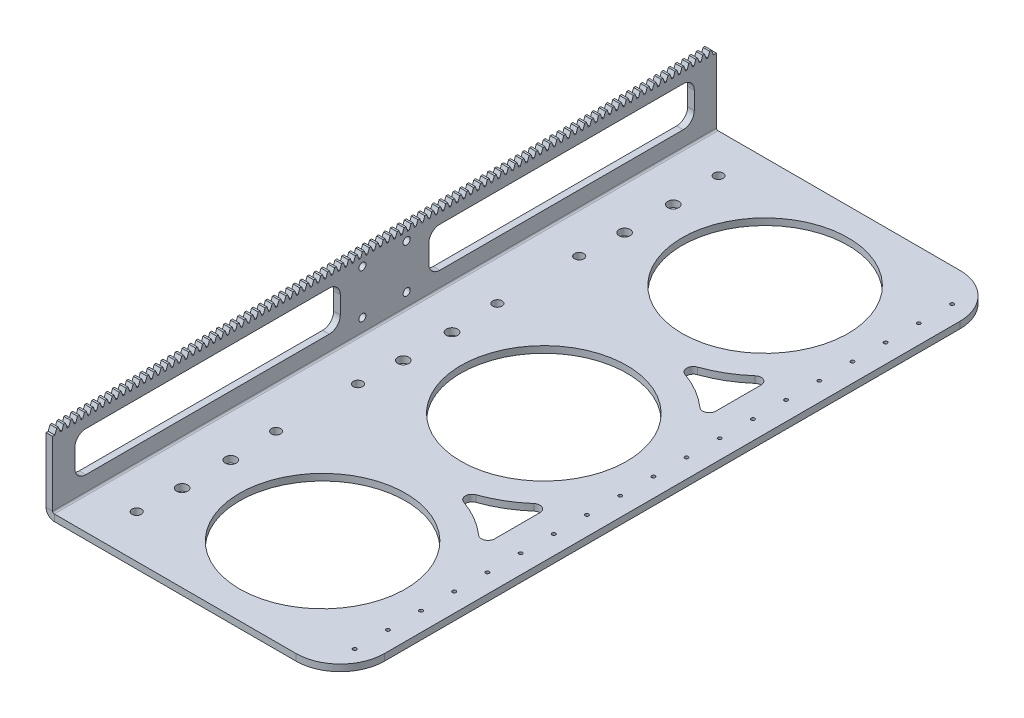
SolidWorks part; units mm, degrees
note: The reader was unsure of these and kept them because the rebuilt part matched: thickness of "基材-凸緣2", "鈑金4", "鈑金6", "鈑金13", "鈑金14", "鈑金15", "鈑金16", "鈑金17", "鈑金18", "鈑金19", "鈑金20", "鈑金21", "鈑金22"; bend radius of "基材彎折1".
material "AISI 304"
ref_plane "前基準面" through (0, 0, 0) normal (0, 0, 1) x (1, 0, 0)
ref_plane "上基準面" through (0, 0, 0) normal (0, 1, 0) x (1, 0, 0)
ref_plane "右基準面" through (0, 0, 0) normal (1, 0, 0) x (0, 0, -1)
sketch "草圖8" plane through (0, 0, 0) normal (0, 0, 1) x (1, 0, 0)
  line L0 (0, 0) -> (0, 30)
  line L1 (0, 0) -> (130, 0)
  dimension "D1" = 130
  dimension "D2" = 30
base flange "基材-凸緣2" sketch "草圖8" end condition mid plane depth 300 reverse direction no thickness 3 reverse thickness direction no bend radius 0.7366
bend "基材彎折1" bend radius 0.7366 bend angle 90 parameters "D5"=1
sketch "草圖18" plane through (-3, 0, 0) normal (-1, 0, 0) x (0, 0, 1)
  line L0 (149, 30) -> (148.1811, 32.25)
  line L1 (148.1811, 32.25) -> (147.3382, 32.25)
  line L2 (147.3382, 32.25) -> (146.5193, 30)
  line L3 (150, 30) -> (-150, 30) construction
  line L4 (146.5193, 30) -> (149, 30)
  line L5 (148.545, 31.25) -> (146.9742, 31.25) construction
  line L7 (150, 30) -> (-150, 30) construction
  dimension "D1" = 2.25
  dimension "D2" = 40
  dimension "D4" = 1.5708
  dimension "D3" = 1
  dimension "D5" = 1
extrude "填料-伸長1" add sketch "草圖18" against normal up to surface (3 mm away) up to face at (0, 15.3683, 0)
sketch "草圖12" plane through (0, 0, 0) normal (0, 1, 0) x (1, 0, 0)
  line L0 (72, 0) -> (130, 0) construction
  line L3 (130, -150) -> (130, 150) construction
  circle A0 centre (72, 0) radius 37.5
  dimension "D1" = 75
  dimension "D2" = 58
extrude "除料-伸長2" cut sketch "草圖12" against normal through all normal cut yes
hole_wizard "M3 餘隙孔1" positions "草圖15" profile "草圖16" hole size "M3" standard "Ansi Metric" end condition through all
sketch "草圖15" plane through (0, 0, 0) normal (1, 0, 0) x (0, 0, -1)
  line L1 (-10, 6.5) -> (10, 6.5) construction
  line L2 (-10, 6.5) -> (-10, 26.5) construction
  line L3 (-10, 26.5) -> (10, 26.5) construction
  line L4 (10, 6.5) -> (10, 26.5) construction
  line L5 (-10, 6.5) -> (10, 26.5) construction
  line L6 (-10, 26.5) -> (10, 6.5) construction
  line L9 (-150, 0.7366) -> (150, 0.7366) construction
  line L10 (0, 0.7366) -> (0, 16.5) construction
  line L12 (-150, 30) -> (-149, 30) construction
  point P2 (10, 26.5)
  point P42 (-10, 26.5)
  point P43 (10, 6.5)
  point P60 (-10, 6.5)
  dimension "D1" = 20
  dimension "D2" = 20
  dimension "D3" = 13.5
sketch "草圖16" plane through (0, 26.5, -10) normal (0, 1, 0) x (0, 0, -1)
  line L0 (0, 0) -> (0, 3)
  line L1 (0, 3) -> (1.6, 3)
  line L2 (1.6, 3) -> (1.6, 0)
  line L5 (1.6, 0) -> (0, 0)
  line L11 (0, -6.35) -> (0, 107.95) construction
  dimension "貫穿孔直徑" = 3.2
  dimension "貫穿孔深度" = 3
pattern_linear "直線複製排列3" count 95 spacing 3.14 along (0, 0, -1) of "填料-伸長1"
pattern_linear "直線複製排列4" count 2 spacing 100 along (0, 0, -1) count 2 spacing 100 along (0, 0, 1) of "除料-伸長2" pattern seed only yes
sketch "草圖19" plane through (0, 0, 0) normal (0, 1, 0) x (1, 0, 0)
  line L3 (130, -150) -> (130, 150) construction
  line L7 (110, 67.5038) -> (110, 32.4962)
  arc A4 (110, 32.4962) -> (72, 50) centre (72, 0) ccw
  arc A5 (110, 67.5038) -> (72, 50) centre (72, 100) cw
  point P6 (0, 0)
  dimension "D2" = 20
extrude "除料-伸長3" cut sketch "草圖19" against normal through all contours L7 A4 A5 normal cut yes
sketch "草圖20" plane through (0, 0, 0) normal (1, 0, 0) x (0, 0, -1)
  line L0 (10, 26.5) -> (10, 6.5) construction
  line L1 (10, 16.5) -> (80, 16.5) construction
  line L2 (150, 30) -> (150, 0.7366) construction
  line L3 (20, 7.5) -> (140, 7.5)
  line L4 (20, 7.5) -> (20, 25.5)
  line L5 (20, 25.5) -> (140, 25.5)
  line L6 (140, 7.5) -> (140, 25.5)
  line L7 (20, 7.5) -> (140, 25.5) construction
  line L8 (20, 25.5) -> (140, 7.5) construction
  dimension "D1" = 10
  dimension "D2" = 120
  dimension "D3" = 18
extrude "除料-伸長4" cut sketch "草圖20" against normal through all normal cut yes
fillet "圓角2" radius 5 4 edges at (-1.5, 25.5, -20) (-1.5, 7.5, -20) (-1.5, 25.5, -140) (-1.5, 7.5, -140)
mirror "鏡射1" about plane through (0, 0, 0) normal (0, 0, 1) of "除料-伸長4", "除料-伸長3", "圓角2"
sketch "草圖21" plane through (0, -3, 0) normal (0, -1, 0) x (1, 0, 0)
  line L0 (19.5, -111) -> (19.5, -89) construction
  line L1 (72, -100) -> (19.5, -100) construction
  line L2 (19.5, -11) -> (19.5, 11) construction
  line L3 (72, 0) -> (19.5, 0) construction
  line L4 (72, 100) -> (19.5, 100) construction
  line L5 (19.5, 111) -> (19.5, 89) construction
  circle A0 centre (19.5, -111) radius 2.5
  circle A1 centre (19.5, -89) radius 2.5
  circle A2 centre (19.5, 11) radius 2.5
  circle A3 centre (19.5, -11) radius 2.5
  circle A4 centre (19.5, 111) radius 2.5
  circle A5 centre (19.5, 89) radius 2.5
  dimension "D1" = 5
  dimension "D2" = 22
  dimension "D3" = 52.5
  dimension "D4" = 3
extrude "除料-伸長5" cut sketch "草圖21" against normal blind 10 normal cut yes
hole_wizard "M4 螺旋的螺孔鑽1" positions "草圖22" profile "草圖23" hole size "M4x0.7" standard "Ansi Metric"
sketch "草圖22" plane through (0, -3, 0) normal (0, -1, 0) x (-1, 0, 0)
  line L0 (-18.5, 132.5) -> (-19.5, 132.5) construction
  line L1 (-19.5, 132.5) -> (-19.5, 111) construction
  line L5 (-18.5, 132.5) -> (-18.5, 69.5) construction
  line L9 (-19.5, 11) -> (-19.5, -11) construction
  line L10 (-18.5, -67.5) -> (-18.5, -130.5) construction
  line L13 (-19.5, -89) -> (-19.5, -111) construction
  line L14 (-18.5, 32.5) -> (-18.5, -30.5) construction
  point P0 (-18.5, 132.5)
  point P16 (-18.5, 69.5)
  point P29 (-18.5, 32.5)
  point P30 (-18.5, -30.5)
  point P56 (-18.5, -67.5)
  point P57 (-18.5, -130.5)
  dimension "D1" = 1
  dimension "D2" = 21.5
  dimension "D3" = 63
  dimension "D5" = 63
  dimension "D6" = 21.5
  dimension "D7" = 1
  dimension "D4" = 21.5
  dimension "D8" = 63
  dimension "D9" = 1
sketch "草圖23" plane through (18.5, -3, -132.5) normal (1, 0, 0) x (0, 0, -1)
  line L0 (0, 0) -> (0, 21.2618)
  line L1 (0, 21.2618) -> (2.1, 20)
  line L2 (2.1, 20) -> (2.1, 0)
  line L5 (2.1, 0) -> (0, 0)
  line L10 (0, 21.2618) -> (-2.1, 20) construction
  line L11 (0, -6.35) -> (0, 107.95) construction
  dimension "鑽孔直徑" = 4.2
  dimension "鑽孔深度" = 20
  dimension "導頭角度" = 118
fillet "圓角3" radius 3 6 edges at (110, -1.5, -32.4962) (110, -1.5, -67.5038) (72, -1.5, -50) (110, -1.5, 32.4962) (72, -1.5, 50) (110, -1.5, 67.5038)
fillet "圓角4" radius 20 2 edges at (130, -1.5, -150) (130, -1.5, 150)
hole_wizard "M2x0.4 螺紋孔1" positions "草圖25" profile "草圖26" tap size "M2x0.4" standard "Ansi Metric" end condition through all
sketch "草圖25" plane through (0, -3, 0) normal (0, -1, 0) x (-1, 0, 0)
  line L0 (-121.5, -135) -> (-121.5, 135) construction
  line L3 (-130, -130) -> (-130, 130) construction
  line L4 (-0.7366, -150) -> (-110, -150) construction
  point P1 (-121.5, -135)
  point P16 (-121.5, -120)
  point P17 (-121.5, -105)
  point P18 (-121.5, -90)
  point P19 (-121.5, -75)
  point P20 (-121.5, -60)
  point P21 (-121.5, -45)
  point P22 (-121.5, -30)
  point P23 (-121.5, -15)
  point P24 (-121.5, 0)
  point P25 (-121.5, 15)
  point P26 (-121.5, 30)
  point P27 (-121.5, 45)
  point P28 (-121.5, 60)
  point P29 (-121.5, 75)
  point P30 (-121.5, 90)
  point P31 (-121.5, 105)
  point P32 (-121.5, 120)
  point P33 (-121.5, 135)
  dimension "D1" = 8.5
  dimension "D2" = 15
  dimension "D3" = 270
  dimension "D5" = 15
  dimension "D4" = 19
sketch "草圖26" plane through (121.5, -3, 135) normal (1, 0, 0) x (0, 0, -1)
  line L0 (0, 0) -> (0, 35.25)
  line L1 (0, 35.25) -> (0.8, 35.25)
  line L2 (0.8, 35.25) -> (0.8, 0)
  line L5 (0.8, 0) -> (0, 0)
  line L11 (0, -6.35) -> (0, 107.95) construction
  dimension "貫穿螺孔鑽直徑" = 1.6
  dimension "貫穿螺孔鑽深度" = 35.25
sketch "彎折-線1" [suppressed] plane through (0, 0, 0) normal (0, 1, 0) x (1, 0, 0)
sketch "邊界方塊1" [suppressed] plane through (0, 0, 0) normal (0, 1, 0) x (1, 0, 0)
sheet metal parameters "鈑金4" thickness 3 parameters "D1"=0.7366
flat pattern "平板-型式4" [suppressed]
sketch "彎折-線3" plane through (0, 0, 0) normal (0, 1, 0) x (1, 0, 0)
  line L0 (-1.02, -150) -> (-1.02, 150) construction
  line L1 (-1.02, -150) -> (-1.02, 150) construction
sketch3d "邊界方塊3" [suppressed]
  line L0 (-32.04, 300, 0) -> (-32.04, 0, 0) construction
  line L1 (120, 300, 0) -> (120, 0, 0) construction
  line L2 (-32.04, 300, 0) -> (120, 300, 0) construction
  line L3 (-32.04, 0, 0) -> (120, 0, 0) construction
bend of the flat pattern "平板-<基材彎折1>1"
sheet metal parameters "鈑金6" thickness 3 parameters "D1"=0.7366
flat pattern "平板-型式4"
sketch "彎折-線3" plane through (0, 0, 0) normal (0, 1, 0) x (1, 0, 0)
  line L0 (-1.02, -150) -> (-1.02, 150) construction
  line L1 (-1.02, -150) -> (-1.02, 150) construction
sketch3d "邊界方塊3" [suppressed]
  line L0 (120.0001, 300, 0) -> (120, 0, 0) construction
  line L1 (-34.29, 300, 0) -> (-34.29, 0, 0) construction
  line L2 (120.0001, 300, 0) -> (-34.29, 300, 0) construction
  line L3 (120, 0, 0) -> (-34.29, 0, 0) construction
bend of the flat pattern "平板-<基材彎折1>1"
sheet metal parameters "鈑金13" thickness 3 parameters "D1"=0.7366
flat pattern "平板-型式4"
sketch "彎折-線3" plane through (0, 0, 0) normal (0, 1, 0) x (1, 0, 0)
  line L0 (-1.8054, -165) -> (-1.8054, 165) construction
  line L1 (-1.8054, -165) -> (-1.8054, 165) construction
sketch3d "邊界方塊3" [suppressed]
  line L0 (-33.6108, 330, 0) -> (-33.6108, 0, 0) construction
  line L1 (150, 330, 0) -> (150, 0, 0) construction
  line L2 (-33.6108, 330, 0) -> (150, 330, 0) construction
  line L3 (-33.6108, 0, 0) -> (150, 0, 0) construction
bend of the flat pattern "平板-<基材彎折1>1"
sheet metal parameters "鈑金14" thickness 3 parameters "D1"=0.7366
flat pattern "平板-型式4"
sketch "彎折-線3" plane through (0, 0, 0) normal (0, 1, 0) x (1, 0, 0)
  line L0 (-1.02, -150) -> (-1.02, 150) construction
  line L1 (-1.02, -150) -> (-1.02, 150) construction
sketch3d "邊界方塊3" [suppressed]
  line L0 (120.0001, 300, 0) -> (120, 0, 0) construction
  line L1 (-34.29, 300, 0) -> (-34.29, 0, 0) construction
  line L2 (120.0001, 300, 0) -> (-34.29, 300, 0) construction
  line L3 (120, 0, 0) -> (-34.29, 0, 0) construction
bend of the flat pattern "平板-<基材彎折1>1"
sheet metal parameters "鈑金15" thickness 3 parameters "D1"=0.7366
flat pattern "平板-型式4"
sketch "彎折-線3" plane through (0, 0, 0) normal (0, 1, 0) x (1, 0, 0)
  line L0 (-1.02, -150) -> (-1.02, 150) construction
  line L1 (-1.02, -150) -> (-1.02, 150) construction
sketch3d "邊界方塊3" [suppressed]
  line L0 (-34.29, 300, 0) -> (-34.29, 0, 0) construction
  line L1 (120, 300, 0) -> (120, 0, 0) construction
  line L2 (-34.29, 300, 0) -> (120, 300, 0) construction
  line L3 (-34.29, 0, 0) -> (120, 0, 0) construction
bend of the flat pattern "平板-<基材彎折1>1"
sheet metal parameters "鈑金16" thickness 3 parameters "D1"=0.7366
flat pattern "平板-型式4"
sketch "彎折-線3" plane through (0, 0, 0) normal (0, 1, 0) x (1, 0, 0)
  line L0 (-1.02, -150) -> (-1.02, 150) construction
  line L1 (-1.02, -150) -> (-1.02, 150) construction
sketch3d "邊界方塊3" [suppressed]
  line L0 (-34.29, 300, 0) -> (-34.29, 0, 0) construction
  line L1 (120, 300, 0) -> (120, 0, 0) construction
  line L2 (-34.29, 300, 0) -> (120, 300, 0) construction
  line L3 (-34.29, 0, 0) -> (120, 0, 0) construction
bend of the flat pattern "平板-<基材彎折1>1"
sheet metal parameters "鈑金17" thickness 3 parameters "D1"=0.7366
flat pattern "平板-型式4"
sketch "彎折-線3" plane through (0, 0, 0) normal (0, 1, 0) x (1, 0, 0)
  line L0 (-1.02, -150) -> (-1.02, 150) construction
  line L1 (-1.02, -150) -> (-1.02, 150) construction
sketch3d "邊界方塊3" [suppressed]
  line L0 (-34.29, 300, 0) -> (-34.29, 0, 0) construction
  line L1 (120, 300, 0) -> (120, 0, 0) construction
  line L2 (-34.29, 300, 0) -> (120, 300, 0) construction
  line L3 (-34.29, 0, 0) -> (120, 0, 0) construction
bend of the flat pattern "平板-<基材彎折1>1"
sheet metal parameters "鈑金18" thickness 3 parameters "D1"=0.7366
flat pattern "平板-型式4"
sketch "彎折-線3" plane through (0, 0, 0) normal (0, 1, 0) x (1, 0, 0)
  line L0 (-1.02, -150) -> (-1.02, 150) construction
  line L1 (-1.02, -150) -> (-1.02, 150) construction
sketch3d "邊界方塊3" [suppressed]
  line L0 (-34.29, 300, 0) -> (-34.29, 0, 0) construction
  line L1 (120, 300, 0) -> (120, 0, 0) construction
  line L2 (-34.29, 300, 0) -> (120, 300, 0) construction
  line L3 (-34.29, 0, 0) -> (120, 0, 0) construction
bend of the flat pattern "平板-<基材彎折1>1"
sheet metal parameters "鈑金19" thickness 3 parameters "D1"=0.7366
flat pattern "平板-型式4"
sketch "彎折-線3" plane through (0, 0, 0) normal (0, 1, 0) x (1, 0, 0)
  line L0 (-1.02, -150) -> (-1.02, 150) construction
  line L1 (-1.02, -150) -> (-1.02, 150) construction
sketch3d "邊界方塊3" [suppressed]
  line L0 (-34.29, 300, 0) -> (-34.29, 0, 0) construction
  line L1 (120, 300, 0) -> (120, 0, 0) construction
  line L2 (-34.29, 300, 0) -> (120, 300, 0) construction
  line L3 (-34.29, 0, 0) -> (120, 0, 0) construction
bend of the flat pattern "平板-<基材彎折1>1"
sheet metal parameters "鈑金20" thickness 3 parameters "D1"=0.7366
flat pattern "平板-型式4"
sketch "彎折-線3" plane through (0, 0, 0) normal (0, 1, 0) x (1, 0, 0)
  line L0 (-1.02, -150) -> (-1.02, 150) construction
  line L1 (-1.02, -150) -> (-1.02, 150) construction
sketch3d "邊界方塊3" [suppressed]
  line L0 (-34.29, 300, 0) -> (-34.29, 0, 0) construction
  line L1 (120, 300, 0) -> (120, 0, 0) construction
  line L2 (-34.29, 300, 0) -> (120, 300, 0) construction
  line L3 (-34.29, 0, 0) -> (120, 0, 0) construction
bend of the flat pattern "平板-<基材彎折1>1"
sheet metal parameters "鈑金21" thickness 3 parameters "D1"=0.7366
flat pattern "平板-型式4"
sketch "彎折-線3" plane through (0, 0, 0) normal (0, 1, 0) x (1, 0, 0)
  line L0 (-1.02, -150) -> (-1.02, 150) construction
  line L1 (-1.02, -150) -> (-1.02, 150) construction
sketch3d "邊界方塊3" [suppressed]
  line L0 (-34.29, 300, 0) -> (-34.29, 0, 0) construction
  line L1 (130, 300, 0) -> (130, 0, 0) construction
  line L2 (-34.29, 300, 0) -> (130, 300, 0) construction
  line L3 (-34.29, 0, 0) -> (130, 0, 0) construction
bend of the flat pattern "平板-<基材彎折1>1"
sheet metal parameters "鈑金22" thickness 3 parameters "D1"=0.7366
flat pattern "平板-型式4"
sketch "彎折-線3" plane through (0, 0, 0) normal (0, 1, 0) x (1, 0, 0)
  line L0 (-1.02, -150) -> (-1.02, 150) construction
  line L1 (-1.02, -150) -> (-1.02, 150) construction
sketch3d "邊界方塊3" [suppressed]
  line L0 (-34.29, 300, 0) -> (-34.29, 0, 0) construction
  line L1 (130, 300, 0) -> (130, 0, 0) construction
  line L2 (-34.29, 300, 0) -> (130, 300, 0) construction
  line L3 (-34.29, 0, 0) -> (130, 0, 0) construction
bend of the flat pattern "平板-<基材彎折1>1"
equation "\"模數\"= 1"
equation "\"D1@草圖18\"=\"模數\"*2.25"
equation "\"D4@草圖18\"=\"模數\"*pi/2"
equation "\"D3@直線複製排列2\"=\"模數\"*PI"
equation "\"D3@草圖18\"=\"模數\"*1"
